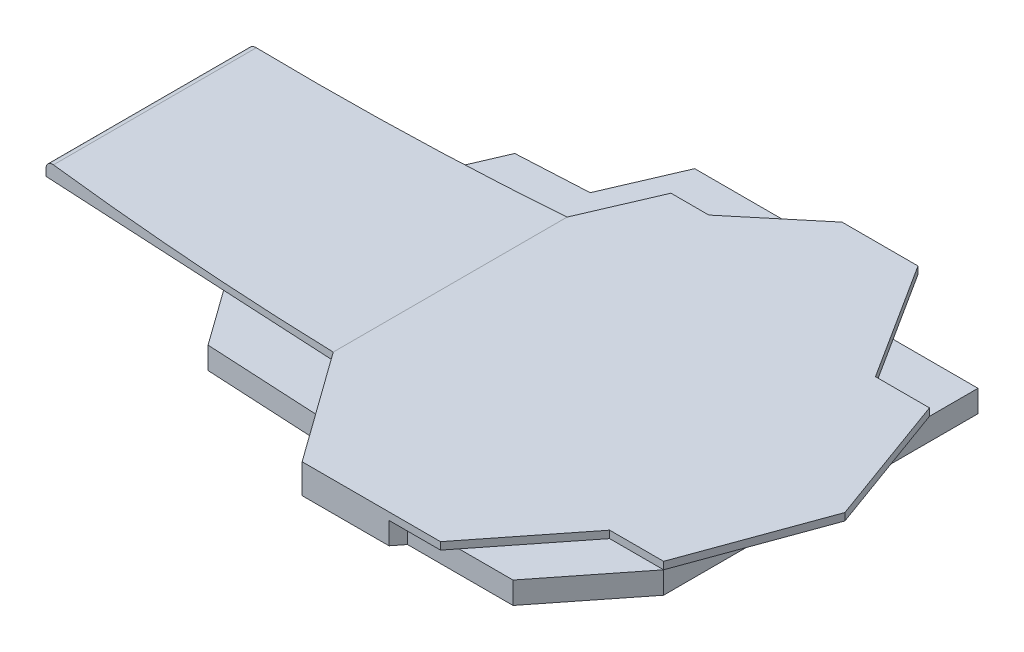
SolidWorks part; units mm, degrees
ref_plane "前视基准面" through (0, 0, 0) normal (0, 0, 1) x (1, 0, 0)
ref_plane "上视基准面" through (0, 0, 0) normal (0, 1, 0) x (1, 0, 0)
ref_plane "右视基准面" through (0, 0, 0) normal (1, 0, 0) x (0, 0, -1)
other "Configuration Table"
sketch "草图2" plane through (0, 0, 0) normal (0, 1, 0) x (1, 0, 0)
  line L0 (0, 0) -> (243.6421, 0) construction
  line L30 (176.8295, 36.1855) -> (82.5273, -31.8251) construction
  line L35 (141.8216, 68.0827) -> (121.1619, 68.0827)
  line L36 (176.8295, 36.1855) -> (190, 0)
  line L37 (104.1466, -61.9173) -> (82.5273, -31.8251)
  line L38 (82.5273, -31.8251) -> (0, -27.5)
  line L39 (0, -27.5) -> (0, 27.5)
  line L40 (0, 27.5) -> (82.5273, 31.8251)
  line L43 (190, 0) -> (176.8295, -36.1855)
  line L45 (82.5273, 31.8251) -> (91.0398, 51.6089)
  line L51 (104.1466, -61.9173) -> (190, 0) construction
  line L53 (141.8216, -61.9173) -> (104.1466, -61.9173)
  line L55 (82.5273, 31.8251) -> (342.4089, 31.8251) construction
  line L57 (176.8295, 36.1855) -> (176.8295, 0) construction
  line L58 (176.8295, 0) -> (176.8295, -36.1855) construction
  line L59 (82.5273, -31.8251) -> (342.4089, -31.8251) construction
  line L62 (91.0398, 51.6089) -> (101.351, 51.6089)
  line L63 (101.351, 51.6089) -> (121.1619, 68.0827)
  line L64 (141.8216, 68.0827) -> (162.1337, 36.1855)
  line L65 (162.1337, 36.1855) -> (176.8295, 36.1855)
  line L66 (176.8295, -36.1855) -> (162.1337, -36.1855)
  line L67 (162.1337, -36.1855) -> (141.8216, -61.9173)
  dimension "D1" = 190
  dimension "D2" = 130
  dimension "D4" = 55
  dimension "D6" = 93
  dimension "D7" = 93
  dimension "D8" = 140
extrude "凸台-拉伸1" add sketch "草图2" along normal blind 2
sketch "草图6" plane through (0, 2, 0) normal (0, 1, 0) x (1, 0, 0)
  line L0 (82.5273, 31.8251) -> (82.5273, -31.8251)
  line L1 (82.5273, -31.8251) -> (0, -27.5)
  line L2 (0, -27.5) -> (0, 27.5)
  line L3 (0, 27.5) -> (82.5273, 31.8251)
extrude "凸台-拉伸2" add sketch "草图6" along normal blind 2
sketch "草图7" plane through (0, 0, 0) normal (0, 0, 1) x (1, 0, 0)
  line L2 (82.5273, 2) -> (82.5273, 30.7408)
  line L3 (82.5273, 30.7408) -> (0, 4)
  spline S0 degree 2 poles (82.5273, 2) (41.2153, 1.0012) (0, 4) knots 0 0 0 1 1 1
extrude "切除-拉伸3" cut sketch "草图7" against normal through all both and the other way through all
fillet "圆角1" radius 2 1 edges at (0, 4, 0)
ref_plane "基准面3" through (0, -12, 0) normal (0, -1, 0) x (-1, 0, 0)
sketch "草图10" plane through (0, 0, 0) normal (0, -1, 0) x (1, 0, 0)
  line L0 (0, 27.5) -> (82.5273, 31.8251)
  line L1 (82.5273, 31.8251) -> (171.8529, 31.8251)
  line L2 (171.8529, 31.8251) -> (171.8529, -31.8251)
  line L3 (171.8529, -31.8251) -> (82.5273, -31.8251)
  line L4 (82.5273, -31.8251) -> (0, -27.5)
  line L5 (0, -27.5) -> (0, 27.5)
sketch "草图12" plane through (0, 2, 0) normal (0, 1, 0) x (1, 0, 0)
  line L0 (176.8295, 36.1855) -> (82.5273, -31.8251)
  line L1 (190, 0) -> (104.1466, -61.9173)
  line L2 (183.4148, 18.0928) -> (93.337, -46.8712) construction
  line L3 (190, 0) -> (176.8295, 36.1855) construction
  line L4 (82.5273, -31.8251) -> (104.1466, -61.9173) construction
sketch "草图13" plane through (0, 0, 0) normal (0, -1, 0) x (1, 0, 0)
  line L0 (53.5015, -30.3039) -> (58.4123, -41.717)
  line L1 (82.5273, -31.8251) -> (0, -27.5) construction
  line L2 (58.4123, -41.717) -> (77.9269, -42.7397)
  line L3 (77.9269, -42.7397) -> (86.4844, -62.6282)
  line L4 (86.4844, -62.6282) -> (136.1647, -62.6282)
  line L7 (136.1647, -62.6282) -> (144.5841, -49.4069)
  line L8 (144.5841, -49.4069) -> (176.8295, -49.4069)
  line L9 (176.8295, -49.4069) -> (176.8295, -36.1855)
  line L10 (176.8295, -36.1855) -> (176.8295, 36.1855)
  line L11 (176.8295, 36.1855) -> (158.7432, 59.0976)
  line L12 (158.7432, 59.0976) -> (130.0164, 59.0976)
  line L13 (130.0164, 59.0976) -> (127.7906, 61.9173)
  line L14 (104.1466, 61.9173) -> (141.8216, 61.9173) construction
  line L15 (127.7906, 61.9173) -> (104.1466, 61.9173)
  line L16 (104.1466, 61.9173) -> (93.337, 46.8712)
  line L17 (93.337, 46.8712) -> (61.8459, 45.2208)
  line L18 (61.8459, 45.2208) -> (51.0363, 30.1747)
  line L19 (0, 27.5) -> (82.5273, 31.8251) construction
  line L20 (51.0363, 30.1747) -> (171.8529, 31.8251)
  line L21 (171.8529, 31.8251) -> (171.8529, -31.8251)
  line L22 (171.8529, -31.8251) -> (53.5015, -30.3039)
extrude "凸台-拉伸4" add sketch "草图13" along normal blind 6 contours L18 L20 L21 L22 L0 L2 L3 L4 L7 L8 L9 L10 L11 L12 L13 L15 L16 L17
